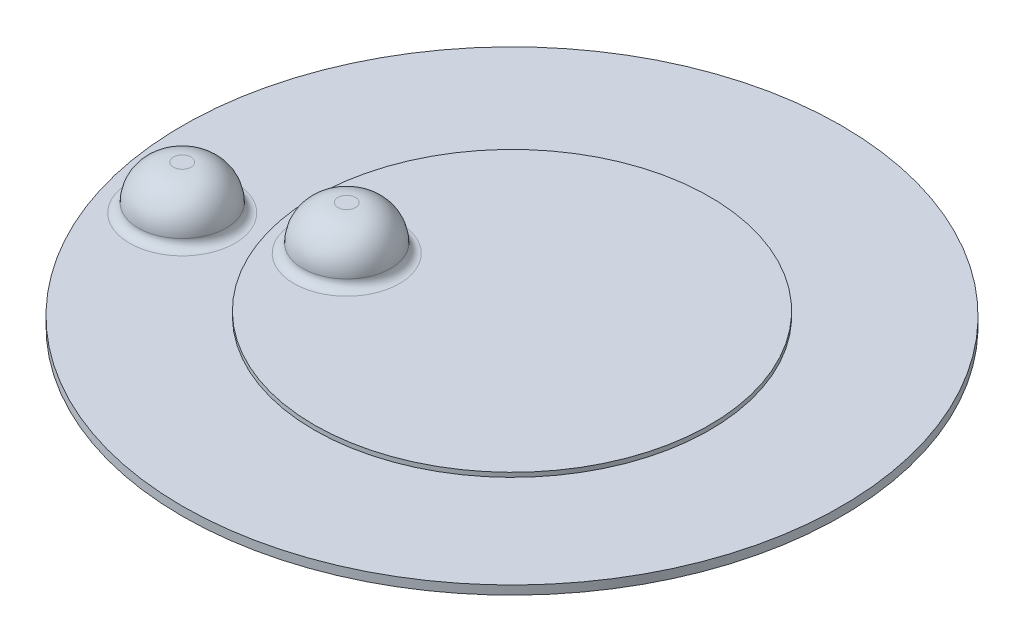
SolidWorks part; units mm, degrees
ref_plane "前视基准面" through (0, 0, 0) normal (0, 0, 1) x (1, 0, 0)
ref_plane "上视基准面" through (0, 0, 0) normal (0, 1, 0) x (1, 0, 0)
ref_plane "右视基准面" through (0, 0, 0) normal (1, 0, 0) x (0, 0, -1)
other "Configuration Table"
sketch "草图1" plane through (0, 0, 0) normal (0, 1, 0) x (1, 0, 0)
  circle A0 centre (0, 0) radius 7.5
  dimension "D1" = 15
extrude "凸台-拉伸1" add sketch "草图1" along normal blind 0.2
sketch "草图2" plane through (0, 0.2, 0) normal (0, 1, 0) x (1, 0, 0)
  circle A0 centre (0, 0) radius 4.5
  dimension "D1" = 9
extrude "凸台-拉伸2" add sketch "草图2" along normal blind 0.1
sketch "草图3" plane through (0, 0.2, 0) normal (0, 1, 0) x (1, 0, 0)
  circle A0 centre (-5.784, -1.721) radius 1
  dimension "D1" = 2
extrude "凸台-拉伸3" add sketch "草图3" along normal blind 1
fillet "圆角1" radius 0.8 1 edges at (-5.784, 1.2, 2.721)
sketch "草图4" plane through (0, 0.3, 0) normal (0, 1, 0) x (1, 0, 0)
  circle A0 centre (-3.0162, -0.7452) radius 1
  dimension "D1" = 2
extrude "凸台-拉伸4" add sketch "草图4" along normal blind 1
fillet "圆角2" radius 0.8 1 edges at (-3.0162, 1.3, 1.7452)
fillet "圆角3" radius 0.2 2 edges at (-3.0162, 0.3, 1.7452) (-5.784, 0.2, 2.721)
